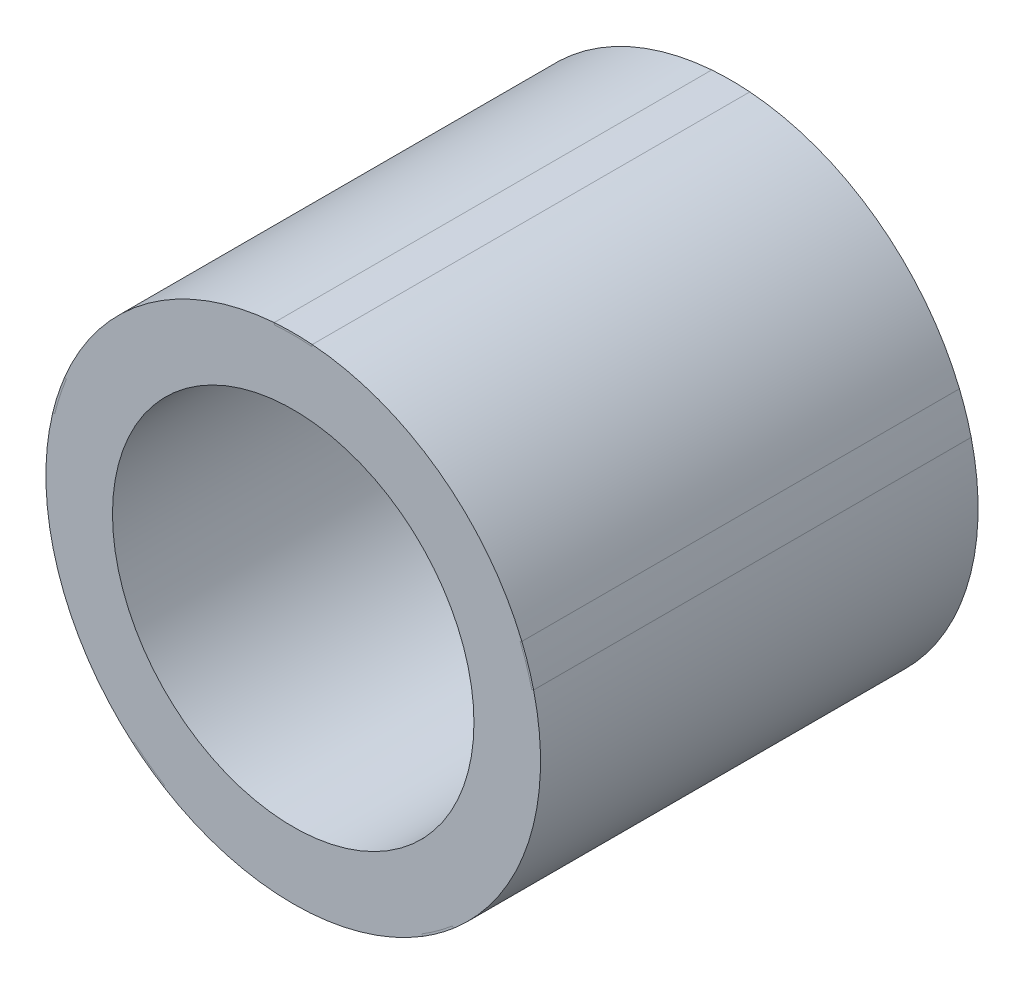
SolidWorks part; units mm, degrees
material "Rubber"
ref_plane "xy" through (0, 0, 0) normal (0, 0, 1) x (1, 0, 0)
ref_plane "xz" through (0, 0, 0) normal (0, 1, 0) x (1, 0, 0)
ref_plane "yz" through (0, 0, 0) normal (1, 0, 0) x (0, 0, -1)
ref_axis "x" through (-14.3, 0, 0) along (1, 0, 0)
ref_axis "y" through (0, 14.3, 0) along (0, -1, 0)
ref_axis "z" through (0, 0, -13.2) along (0, 0, 1)
sketch "Sketch1" plane through (0, 0, 0) normal (0, 0, 1) x (1, 0, 0)
  circle A0 centre (0, 0) radius 9.5
  dimension "D1" = 19
extrude "Extrude-Thin1" add sketch "Sketch1" along normal mid plane 23 thin thin type one direction wall 3.5
sketch "Sketch2" plane through (0, 0, 0) normal (0, 0, 1) x (1, 0, 0)
  line L0 (1, 12.9615) -> (0.9923, 12.8618)
  line L1 (-1, 12.9615) -> (-0.9923, 12.8618)
  arc A0 (-1, 12.9615) -> (1, 12.9615) centre (0, 0) cw
  arc A1 (-0.9923, 12.8618) -> (0.9923, 12.8618) centre (0, 0) cw
  circle A2 centre (0, 0) radius 13 construction
  dimension "D1" = 0.1
  dimension "D2" = 2
extrude "Cut-Extrude1" cut sketch "Sketch2" against normal through all and the other way through all
extrude "Boss-Extrude1" add sketch "Sketch2<2>" along normal mid plane 23 separate body
sketch "Sketch2<2>" plane through (0, 0, 0) normal (0, 0, 1) x (1, 0, 0) same geometry as "Sketch2"
pattern_circular "CirPattern1" count 5 over 360 about axis through (0, 0, -13.2) along (0, 0, 1) of "Cut-Extrude1"
pattern_circular "CirPattern3" count 5 over 360 about axis through (0, 0, -13.2) along (0, 0, 1) of bodies 104
